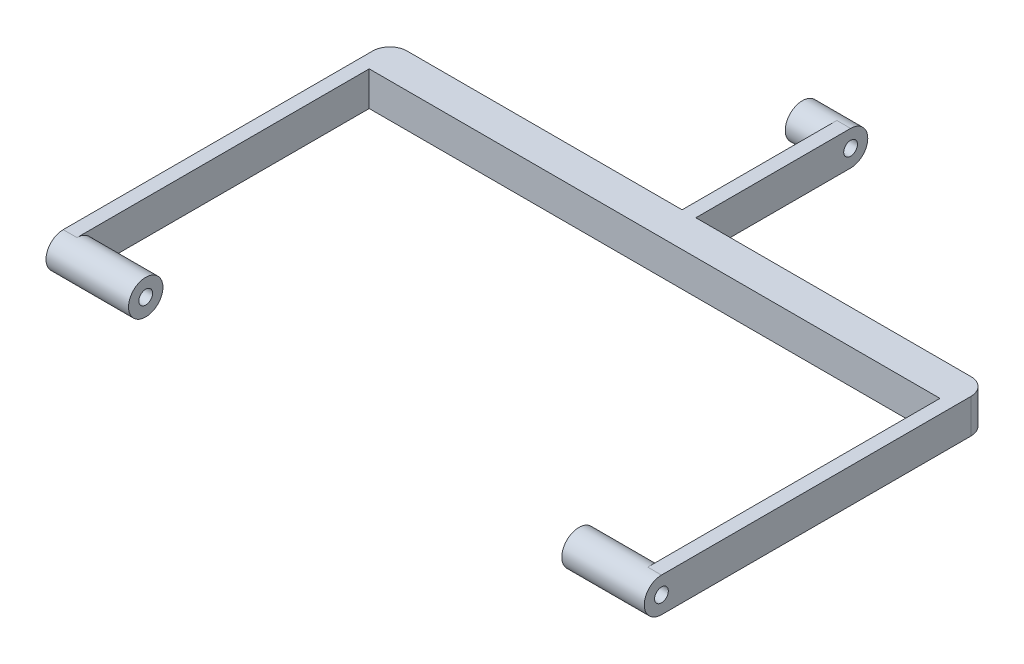
SolidWorks part; units mm, degrees
ref_plane "Plano frontal" through (0, 0, 0) normal (0, 0, 1) x (1, 0, 0)
ref_plane "Plano superior" through (0, 0, 0) normal (0, 1, 0) x (1, 0, 0)
ref_plane "Plano direito" through (0, 0, 0) normal (1, 0, 0) x (0, 0, -1)
sketch "Esboço1" plane through (0, 0, 0) normal (0, 1, 0) x (1, 0, 0)
  line L1 (-43.5, -2.5) -> (43.5, -2.5)
  line L2 (-43.5, -2.5) -> (-43.5, 2.5)
  line L3 (-43.5, 2.5) -> (43.5, 2.5)
  line L4 (43.5, -2.5) -> (43.5, 2.5)
  line L5 (-43.5, -2.5) -> (43.5, 2.5) construction
  line L6 (-43.5, 2.5) -> (43.5, -2.5) construction
  point P0 (0, 0)
  dimension "D1" = 87
  dimension "D2" = 5
extrude "Ressalto-extrusão1" add sketch "Esboço1" along normal blind 5
sketch "Esboço2" plane through (0, 0, 0) normal (0, 1, 0) x (1, 0, 0)
  line L1 (-43.5, 2.5) -> (-41.5, 2.5)
  line L2 (-43.5, 2.5) -> (-43.5, -47.5)
  line L3 (-43.5, -47.5) -> (-41.5, -47.5)
  line L4 (-41.5, 2.5) -> (-41.5, -47.5)
  dimension "D1" = 2
  dimension "D2" = 50
extrude "Ressalto-extrusão2" add sketch "Esboço2" along normal blind 5
fillet "Filete1" radius 2.5 2 edges at (-42.5, 0, 47.5) (-42.5, 5, 47.5)
sketch "Esboço6" plane through (-41.5, 0, 0) normal (1, 0, 0) x (0, 0, -1)
  circle A0 centre (-45, 2.5) radius 2.5
  arc A1 (-47.5, 2.5) -> (-45, 0) centre (-45, 2.5) ccw construction
extrude "Ressalto-extrusão4" add sketch "Esboço6" along normal blind 10
sketch "Esboço7" plane through (-31.5, 0, 0) normal (1, 0, 0) x (0, 0, -1)
  circle A0 centre (-45, 2.5) radius 1
  circle A1 centre (-45, 2.5) radius 2.5 construction
  dimension "D1" = 2
extrude "Corte-extrusão3" cut sketch "Esboço7" against normal through all
mirror "Espelhar1" about plane through (0, 0, 0) normal (1, 0, 0) of "Corte-extrusão3", "Ressalto-extrusão4", "Filete1", "Ressalto-extrusão2"
fillet "Filete2" radius 2.5 2 edges at (43.5, 2.5, -2.5) (-43.5, 2.5, -2.5)
sketch "Esboço4" plane through (0, 0, 0) normal (1, 0, 0) x (0, 0, -1)
  line L0 (-45, 5) -> (0, 5) construction
  line L1 (-2.5, 5) -> (27.5, 5)
  line L2 (-2.5, 5) -> (-2.5, 0)
  line L3 (-2.5, 0) -> (27.5, 0)
  line L4 (27.5, 5) -> (27.5, 0)
  line L5 (2.5, 5) -> (2.5, 0) construction
  dimension "D1" = 30
  dimension "D2" = 5
  dimension "D3" = 5
extrude "Ressalto-extrusão3" add sketch "Esboço4" along normal mid plane 2
fillet "Filete3" radius 2.5 2 edges at (0, 5, -27.5) (0, 0, -27.5)
sketch "Esboço8" plane through (-1, 0, 0) normal (-1, 0, 0) x (0, 0, 1)
  circle A0 centre (-25, 2.5) radius 2.5
  arc A1 (-27.5, 2.5) -> (-25, 0) centre (-25, 2.5) ccw construction
extrude "Ressalto-extrusão5" add sketch "Esboço8" along normal blind 5
sketch "Esboço5" plane through (0, 0, 0) normal (1, 0, 0) x (0, 0, -1)
  circle A0 centre (25, 2.5) radius 1
  arc A2 (27.5, 2.5) -> (25, 5) centre (25, 2.5) ccw construction
  dimension "D1" = 2
extrude "Corte-extrusão2" cut sketch "Esboço5" against normal through all both and the other way through all
